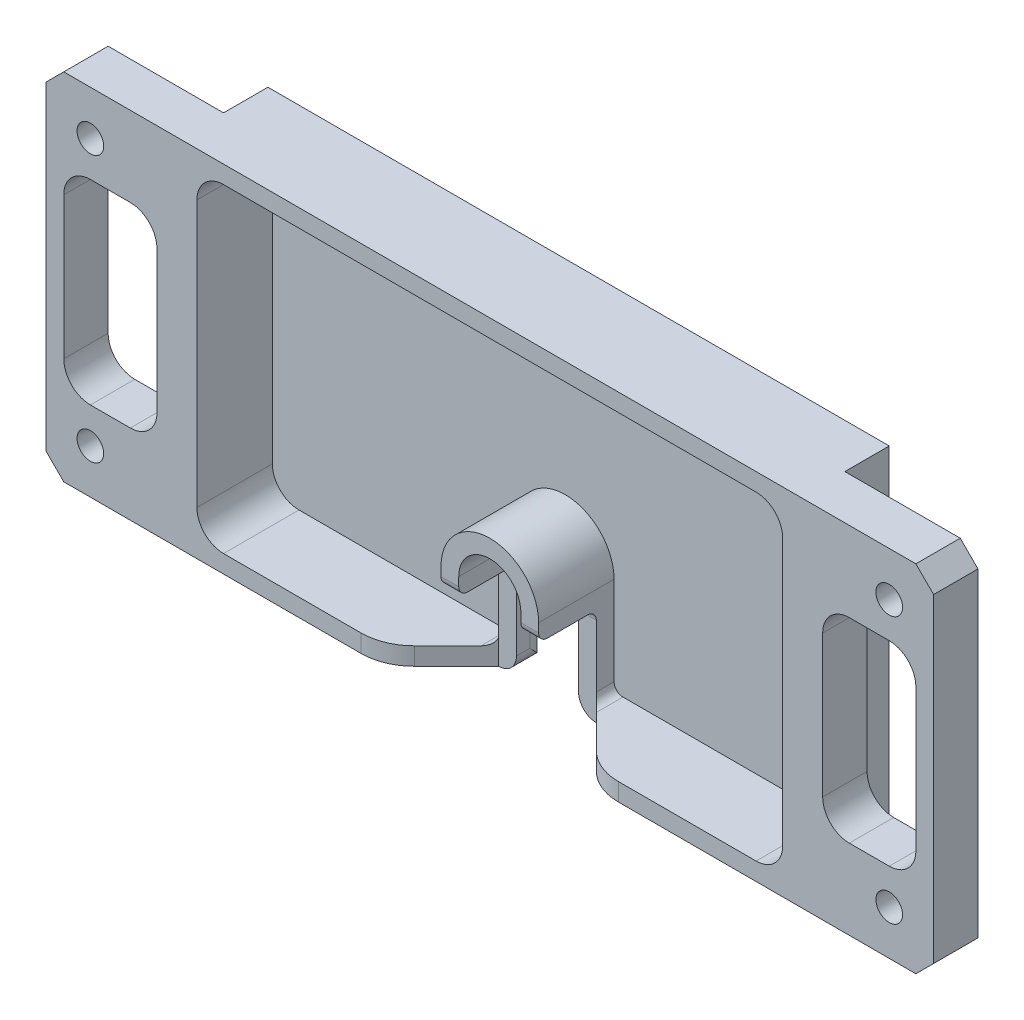
SolidWorks part; units mm, degrees
material "ABS"
ref_plane "Ebene vorne" through (0, 0, 0) normal (0, 0, 1) x (1, 0, 0)
ref_plane "Ebene oben" through (0, 0, 0) normal (0, 1, 0) x (1, 0, 0)
ref_plane "Ebene rechts" through (0, 0, 0) normal (1, 0, 0) x (0, 0, -1)
sketch "Skizze1" plane through (0, 0, 0) normal (0, 0, 1) x (1, 0, 0)
  line L0 (0, 52.8107) -> (0, -52.2189) construction
  line L1 (-65.5195, 0) -> (67.0248, 0) construction
  line L2 (-50, -20) -> (-50, 20)
  line L3 (-50, 20) -> (50, 20)
  line L4 (50, -20) -> (50, 20)
  line L5 (-50, -20) -> (50, -20)
  point P9 (0, 20)
  point P10 (0, -20)
  point P12 (50, 0)
  point P13 (-50, 0)
  dimension "D1" = 40
  dimension "D2" = 100
extrude "Aufsatz-Linear austragen1" add sketch "Skizze1" along normal blind 2.5 and the other way blind 2.5
sketch "Skizze2" plane through (0, 0, 0) normal (0, 0, 1) x (1, 0, 0)
  line L0 (0, 30.9245) -> (0, -26.0823) construction
  line L1 (-65.8109, 0) -> (54.5857, 0) construction
  circle A0 centre (-45, 15) radius 1.5
  circle A1 centre (-45, -15) radius 1.5
  circle A2 centre (45, -15) radius 1.5
  circle A3 centre (45, 15) radius 1.5
  dimension "D3" = 3
  dimension "D1" = 30
  dimension "D2" = 90
extrude "Schnitt-Linear austragen1" cut sketch "Skizze2" against normal through all and the other way through all
sketch "Skizze4" plane through (0, 0, 0) normal (0, 0, 1) x (1, 0, 0)
  line L0 (0, 35.9786) -> (0, -30.5696) construction
  line L1 (-57.4553, 0) -> (60.3332, 0) construction
  line L2 (-48, -8) -> (-48, 8)
  line L3 (-45, 11) -> (-40.5, 11)
  line L4 (-37.5, 8) -> (-37.5, -8)
  line L5 (-45, -11) -> (-40.5, -11)
  line L6 (45, -11) -> (40.5, -11)
  line L7 (37.5, 8) -> (37.5, -8)
  line L8 (45, 11) -> (40.5, 11)
  line L9 (48, -8) -> (48, 8)
  arc A0 (-37.5, -8) -> (-40.5, -11) centre (-40.5, -8) cw
  arc A1 (-45, -11) -> (-48, -8) centre (-45, -8) cw
  arc A2 (-37.5, 8) -> (-40.5, 11) centre (-40.5, 8) ccw
  arc A3 (-48, 8) -> (-45, 11) centre (-45, 8) cw
  arc A4 (48, 8) -> (45, 11) centre (45, 8) ccw
  arc A5 (37.5, 8) -> (40.5, 11) centre (40.5, 8) cw
  arc A6 (45, -11) -> (48, -8) centre (45, -8) ccw
  arc A7 (37.5, -8) -> (40.5, -11) centre (40.5, -8) ccw
  point P10 (-37.5, 0)
  point P11 (-48, 0)
  point P13 (-37.5, -11)
  point P16 (-48, -11)
  point P19 (-37.5, 11)
  point P22 (-48, 11)
  point P35 (48, 0)
  point P36 (37.5, 0)
  dimension "D4" = 3
  dimension "D1" = 22
  dimension "D2" = 48
  dimension "D3" = 37.5
extrude "Schnitt-Linear austragen2" cut sketch "Skizze4" against normal through all and the other way through all
sketch "Skizze7" plane through (0, 0, -2.5) normal (0, 0, -1) x (-1, 0, 0)
  line L0 (0, 37.0279) -> (0, -33.8129) construction
  line L1 (-65.6302, 0) -> (60.974, 0) construction
  line L2 (-35, 20) -> (-35, -20)
  line L3 (-50, 20) -> (50, 20) construction
  line L4 (-35, 20) -> (35, 20)
  line L6 (35, 20) -> (35, -20)
  line L7 (-35, -20) -> (35, -20)
  line L8 (-33, 18) -> (-33, -18) construction
  line L9 (-33, -18) -> (33, -18) construction
  line L10 (33, 18) -> (33, -18) construction
  line L11 (-33, 18) -> (33, 18) construction
  point P13 (0, 20)
  point P14 (0, -20)
  point P16 (35, 0)
  point P17 (-35, 0)
  dimension "D2" = 70
  dimension "D1" = 2
extrude "Aufsatz-Linear austragen3" add sketch "Skizze7" along normal blind 5
chamfer "Fase1" distance 2 angle 45 4 edges at (-50, 20, 0) (-50, -20, 0) (50, 20, 0) (50, -20, 0)
sketch "Skizze9" plane through (0, 0, 0) normal (0, 0, 1) x (1, 0, 0)
  line L0 (0, -49.6871) -> (0, 45.5195) construction
  line L1 (59.7508, 0) -> (-59.778, 0) construction
  line L2 (-3.5, -20) -> (3.5, -20)
  line L3 (3.5, -20) -> (3.5, -7)
  line L4 (-48, -20) -> (48, -20) construction
  line L5 (-3.5, -20) -> (-3.5, -7)
  arc A0 (3.5, -7) -> (-3.5, -7) centre (0, -7) ccw
  point P14 (0, -20)
  dimension "D1" = 7
  dimension "D2" = 13
extrude "Schnitt-Linear austragen7" cut sketch "Skizze9" against normal through all and the other way through all
fillet "Verrundung1" radius 2 2 edges at (-3.5, -20, -2.5) (3.5, -20, -2.5)
sketch "Skizze8" plane through (0, 0, 2.5) normal (0, 0, 1) x (1, 0, 0)
  line L0 (0, 38.5492) -> (0, -31.5223) construction
  line L1 (-74.5556, 0) -> (52.9258, 0) construction
  line L11 (6.5, -18) -> (30, -18)
  line L13 (-5.5, -7) -> (-5.5, -18)
  line L14 (33, -15) -> (33, 15)
  line L15 (-30, -18) -> (-6.5, -18)
  line L16 (-33, 15) -> (-33, -15)
  line L17 (30, 18) -> (-30, 18)
  line L18 (5.5, -18) -> (5.5, -7)
  line L19 (-5.5, -7) -> (-5.5, -17)
  line L20 (5.5, -17) -> (5.5, -7)
  arc A0 (30, 18) -> (33, 15) centre (30, 15) cw
  arc A1 (-30, -18) -> (-33, -15) centre (-30, -15) cw
  arc A2 (30, -18) -> (33, -15) centre (30, -15) ccw
  arc A3 (-6.5, -18) -> (-5.5, -17) centre (-6.5, -17) ccw
  arc A4 (5.5, -17) -> (6.5, -18) centre (6.5, -17) ccw
  arc A11 (5.5, -7) -> (-5.5, -7) centre (0, -7) ccw
  arc A15 (-30, 18) -> (-33, 15) centre (-30, 15) ccw
  arc A16 (5.5, -7) -> (-5.5, -7) centre (0, -7) ccw
  dimension "D3" = 3
  dimension "D1" = 1
  dimension "D2" = 66
  dimension "D4" = 2
extrude "Schnitt-Linear austragen6" cut sketch "Skizze8" against normal offset from surface (8.5 mm away) 1.5 up to face at (0, -8.7328, -7.5)
fillet "Verrundung2" radius 2 3 edges at (-3.5, -12.5, -7.5) (3.5, -12.5, -7.5) (0, -3.5, -7.5) tangent propagation no
ref_plane "Ebene1" through (0, -9, 0) normal (0, 1, 0) x (1, 0, 0)
sketch "Skizze10" plane through (0, -9, 0) normal (0, 1, 0) x (1, 0, 0)
  line L0 (0, -19.2045) -> (0, 18.8576) construction
  line L1 (29.7352, 0) -> (-26.7651, 0) construction
  line L2 (12, -2.5) -> (5.5, 4)
  line L3 (5.5, 4) -> (-5.5, 4)
  line L4 (12, -2.5) -> (-12, -2.5)
  line L5 (6.5, -2.5) -> (30, -2.5) construction
  line L7 (-12, -2.5) -> (-5.5, 4)
  line L8 (-6.5, 6) -> (-30, 6) construction
  point P14 (0, -2.5)
  point P15 (0, 6)
  dimension "D1" = 24
  dimension "D2" = 11
  dimension "D3" = 2
extrude "Schnitt-Linear austragen8" cut sketch "Skizze10" against normal through all
fillet "Verrundung3" radius 1 4 edges at (-4.5, -9, -4) (-4.5, -9, 2.5) (4.5, -9, 2.5) (4.5, -9, -4)
fillet "Verrundung4" radius 6 2 edges at (12, -19, 2.5) (-12, -19, 2.5)
